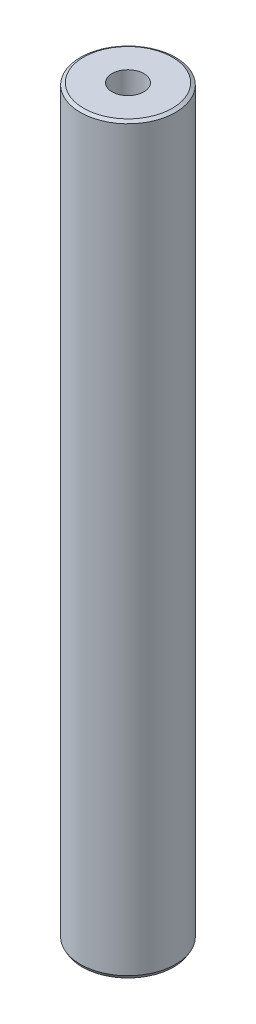
SolidWorks part; units mm, degrees
ref_plane "Front Plane" through (0, 0, 0) normal (0, 0, 1) x (1, 0, 0)
ref_plane "Top Plane" through (0, 0, 0) normal (0, 1, 0) x (1, 0, 0)
ref_plane "Right Plane" through (0, 0, 0) normal (1, 0, 0) x (0, 0, -1)
sketch "Sketch1" plane through (0, 0, 0) normal (0, 1, 0) x (1, 0, 0)
  circle A0 centre (0, 0) radius 32.5
  dimension "SHAFT_OD" = 65
extrude "Boss-Extrude1" add sketch "Sketch1" along normal blind 506.7841
sketch "Sketch2" plane through (0, 0, 0) normal (0, 1, 0) x (1, 0, 0)
  circle A0 centre (0, 0) radius 10.8421
  dimension "BORE_D" = 21.6842
extrude "Cut-Extrude1" cut sketch "Sketch2" along normal through all
chamfer "Chamfer1" distance 1.3048 angle 60 2 edges at (0, 506.7841, 32.5) (0, 0, 32.5) first distance on face at (0, 506.7841, 32.5) first distance on face at (0, 0, 10.8421)
